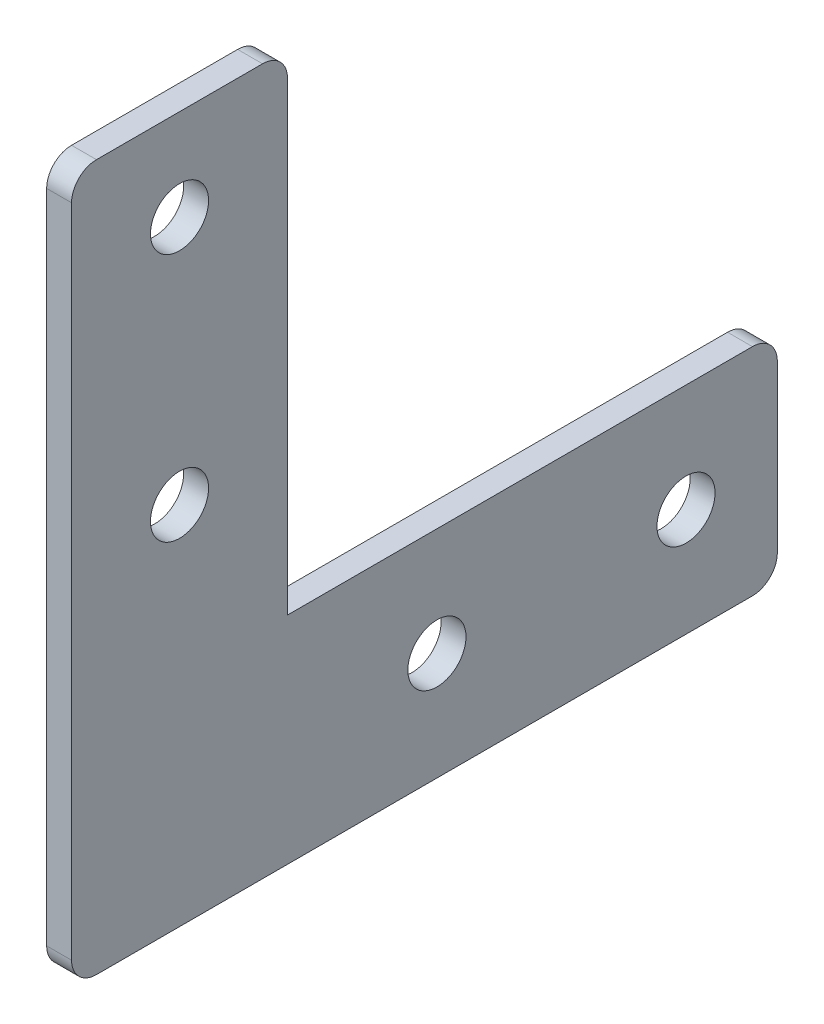
SolidWorks part; units mm, degrees
note: '?' marks a value the reader was unsure of.
ref_plane "Front Plane" through (0, 0, 0) normal (0, 0, 1) x (1, 0, 0)
ref_plane "Top Plane" through (0, 0, 0) normal (0, 1, 0) x (1, 0, 0)
ref_plane "Right Plane" through (0, 0, 0) normal (1, 0, 0) x (0, 0, -1)
ref_axis "Axis_X" through (-88.99, 0, 0) along (1, 0, 0)?
ref_axis "Axis_Y" through (0, 55, 0) along (0, -1, 0)?
ref_axis "Axis_Z" through (0, 0, -88.99) along (0, 0, 1)?
sketch "Sketch1" plane through (0, 0, 0) normal (1, 0, 0) x (0, 0, -1)
  line L1 (0, 0) -> (85, 0)
  line L2 (0, 0) -> (0, 85)
  line L3 (0, 85) -> (85, 85)
  line L4 (85, 0) -> (85, 85)
  line L5 (0, 0) -> (85, 85) construction
  line L6 (0, 85) -> (85, 0) construction
  point P0 (0, 0)
  dimension "L" = 85
extrude "Boss-Extrude1" add sketch "Sketch1" along normal blind 3
sketch "Sketch2" plane through (0, 0, 0) normal (1, 0, 0) x (0, 0, -1)
  line L0 (26, 85) -> (26, 26)
  line L1 (85, 85) -> (0, 85) construction
  line L2 (26, 26) -> (85, 26)
  line L3 (0, 85) -> (0, 0) construction
  line L4 (85, 0) -> (85, 85) construction
  line L5 (85, 26) -> (85, 85)
  line L6 (85, 85) -> (26, 85)
  dimension "H" = 59
  dimension "W" = 26
extrude "Cut-Extrude1" cut sketch "Sketch2" along normal through all
hole_wizard "DiameterHole1" positions "Sketch4" profile "Sketch3" hole size "Ø7.0" standard "JIS" end condition through all
sketch "Sketch4" plane through (3, 0, 0) normal (1, 0, 0) x (0, 0, -1)
  line L0 (13, 85) -> (13, 0) construction
  line L1 (26, 85) -> (0, 85) construction
  line L2 (0, 0) -> (85, 0) construction
  line L4 (85, 13) -> (0, 13) construction
  line L5 (85, 0) -> (85, 26) construction
  line L6 (0, 85) -> (0, 0) construction
  point P0 (13, 74)
  point P2 (13, 44)
  point P4 (74, 13)
  point P6 (44, 13)
sketch "Sketch3" plane through (3, 74, -13) normal (0, 1, 0) x (0, 0, -1)
  line L0 (0, 0) -> (0, 3)
  line L1 (0, 3) -> (3.5, 3)
  line L2 (3.5, 3) -> (3.5, 0)
  line L5 (3.5, 0) -> (0, 0)
  line L11 (0, -6.35) -> (0, 107.95) construction
  dimension "D" = 7
  dimension "Thru Hole Depth" = 3
sketch "Sketch5" plane through (0, 0, 0) normal (1, 0, 0) x (0, 0, -1)
  line L0 (42.5, 0) -> (42.5, 85) construction
  line L1 (0, 0) -> (85, 0) construction
  line L3 (0, 85) -> (29.5, 85)
  line L4 (26, 85) -> (0, 85) construction
  line L5 (29.5, 85) -> (29.5, 26)
  line L7 (29.5, 26) -> (0, 26)
  line L8 (0, 85) -> (0, 0) construction
  line L9 (0, 26) -> (0, 85)
  line L10 (85, 26) -> (85, 85)
  line L11 (55.5, 26) -> (85, 26)
  line L12 (26, 85) -> (0, 85) construction
  line L13 (55.5, 85) -> (55.5, 26)
  line L14 (85, 85) -> (55.5, 85)
  dimension "W" = 26
  dimension "H" = 59
extrude "Cut-Extrude2" [suppressed] cut sketch "Sketch5" along normal through all
hole_wizard "DiameterHole2" [suppressed] positions "Sketch7" profile "Sketch6" hole size "Ø7.0" standard "JIS"
sketch "Sketch7" plane through (3, 0, 0) normal (1, 0, 0) x (0, 0, -1)
  line L0 (42.5, 85) -> (42.5, 0) construction
  line L1 (55.5, 85) -> (29.5, 85) construction
  line L2 (0, 0) -> (85, 0) construction
  line L4 (0, 13) -> (85, 13) construction
  line L5 (0, 26) -> (0, 0) construction
  line L6 (85, 0) -> (85, 26) construction
  point P0 (42.5, 74)
  point P2 (42.5, 44)
  point P4 (11, 13)
  point P6 (73, 13)
  dimension "L2" = 30
  dimension "L1" = 62
sketch "Sketch6" plane through (3, 74, -42.5) normal (0, 1, 0) x (0, 0, -1)
  line L0 (0, 0) -> (0, 3)
  line L1 (0, 3) -> (3.5, 3)
  line L2 (3.5, 3) -> (3.5, 0)
  line L5 (3.5, 0) -> (0, 0)
  line L11 (0, -6.35) -> (0, 107.95) construction
  dimension "D" = 7
  dimension "Thru Hole Depth" = 3
fillet "Fillet1" radius 3 5 edges at (1.5, 0, -85) (1.5, 0, 0) (1.5, 85, 0) (1.5, 26, -85) (1.5, 85, -26)
fillet "Fillet2" [suppressed] radius 3
equation "\"Factor\"= 1.082532"
